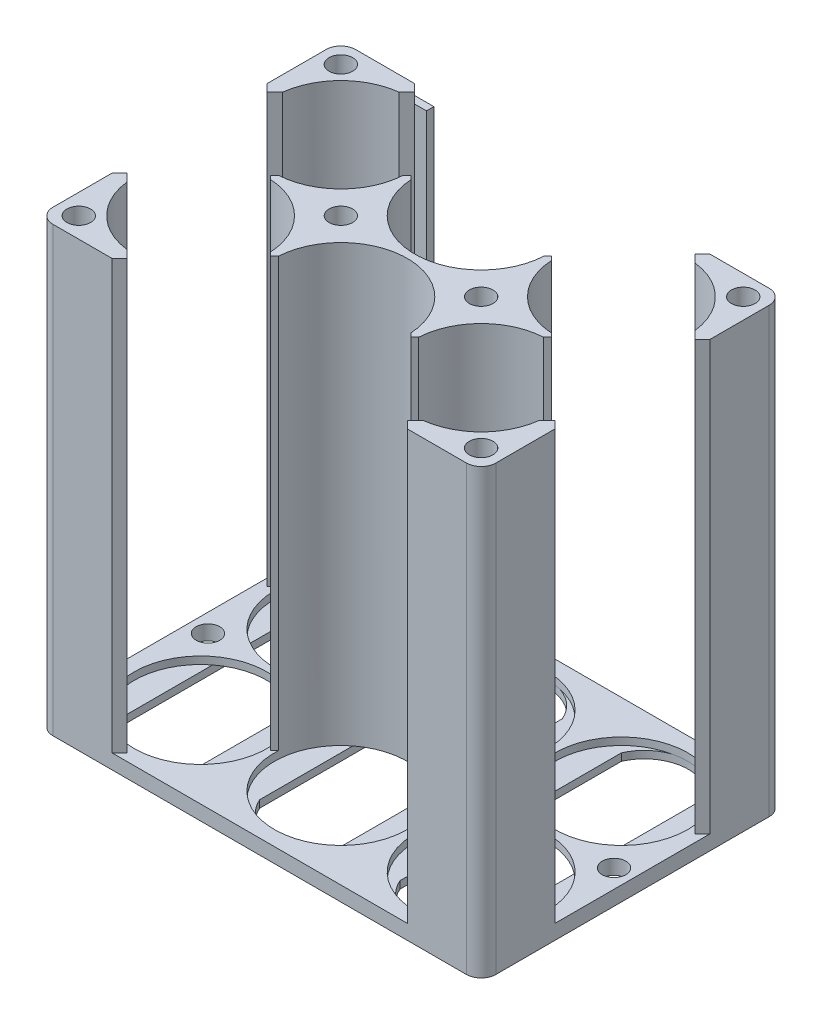
SolidWorks part; units mm, degrees
ref_plane "Płaszczyzna przednia" through (0, 0, 0) normal (0, 0, 1) x (1, 0, 0)
ref_plane "Płaszczyzna górna" through (0, 0, 0) normal (0, 1, 0) x (1, 0, 0)
ref_plane "Płaszczyzna prawa" through (0, 0, 0) normal (1, 0, 0) x (0, 0, -1)
sketch "Sketch1" plane through (0, 0, 0) normal (0, 1, 0) x (1, 0, 0)
  line L1 (0, 0) -> (-60, 0)
  line L2 (0, 0) -> (0, 41)
  line L3 (0, 41) -> (-60, 41)
  line L4 (-60, 0) -> (-60, 41)
  line L5 (0, 0) -> (-60, 41) construction
  line L6 (0, 41) -> (-60, 0) construction
  point P4 (-30, 20.5)
  dimension "D1" = 41
  dimension "D2" = 60
extrude "Boss-Extrude1" add sketch "Sketch1" along normal blind 2
sketch "Sketch2" plane through (0, 2, 0) normal (0, 1, 0) x (1, 0, 0)
  line L0 (-60, 41) -> (-60, 0) construction
  line L1 (-60, 0) -> (0, 0) construction
  circle A0 centre (-49, 11) radius 9
  circle A1 centre (-30, 11) radius 9
  circle A2 centre (-11, 11) radius 9
  circle A3 centre (-30, 30) radius 9
  circle A4 centre (-11, 30) radius 9
  circle A5 centre (-49, 30) radius 9
  dimension "D1" = 18
  dimension "D2" = 11
  dimension "D3" = 11
  dimension "D4" = 3
  dimension "D5" = 2
extrude "Cut-Extrude2" cut sketch "Sketch2" against normal blind 1 contours A0 | A1 | A5 | A3 | A4 | A2
sketch "Sketch3" plane through (0, 0, 0) normal (0, -1, 0) x (1, 0, 0)
  line L0 (0, -41) -> (-60, -41) construction
  line L2 (-5.5, -35.4979) -> (-5.5, -5.4979)
  line L4 (-16.5, -35.4979) -> (-16.5, -5.4979)
  line L5 (-5.5, -35.4979) -> (-16.5, -5.4979) construction
  line L6 (-5.5, -5.4979) -> (-16.5, -35.4979) construction
  line L7 (-60, 0) -> (0, 0) construction
  line L9 (0, 0) -> (0, -41) construction
  line L10 (-35.5, -35.4979) -> (-35.5, -5.4979)
  line L11 (-24.5, -35.4979) -> (-24.5, -5.4979)
  line L12 (-54.5, -35.4979) -> (-54.5, -5.4979)
  line L13 (-43.5, -35.4979) -> (-43.5, -5.4979)
  line L14 (-60, -41) -> (-60, 0) construction
  arc A0 (-5.5, -5.4979) -> (-16.5, -5.4979) centre (-11, -7.8958) ccw
  arc A1 (-5.5, -35.4979) -> (-16.5, -35.4979) centre (-11, -33.1) cw
  arc A2 (-24.5, -5.4979) -> (-35.5, -5.4979) centre (-30, -7.8958) ccw
  arc A3 (-24.5, -35.4979) -> (-35.5, -35.4979) centre (-30, -33.1) cw
  arc A4 (-43.5, -5.4979) -> (-54.5, -5.4979) centre (-49, -7.8958) ccw
  arc A5 (-43.5, -35.4979) -> (-54.5, -35.4979) centre (-49, -33.1) cw
  point P4 (-11, -20.4979)
  dimension "D2" = 6
  dimension "D3" = 6
  dimension "D5" = 7.9
  dimension "D6" = 7.8958
  dimension "D1" = 11
  dimension "D4" = 30
  dimension "D7" = 5.5
  dimension "D9" = 5.5
  dimension "D8" = 3
extrude "Cut-Extrude3" cut sketch "Sketch3" against normal blind 1
sketch "Sketch4" plane through (0, 0, 0) normal (0, -1, 0) x (1, 0, 0)
  line L0 (-16.5, -5.4979) -> (-16.5, -35.4979) construction
  line L1 (-16.5, -24.5011) -> (-24.5, -24.5011)
  line L2 (-16.5, -24.5011) -> (-16.5, -16.5011)
  line L3 (-16.5, -16.5011) -> (-24.5, -16.5011)
  line L4 (-24.5, -24.5011) -> (-24.5, -16.5011)
  line L5 (-16.5, -24.5011) -> (-24.5, -16.5011) construction
  line L6 (-16.5, -16.5011) -> (-24.5, -24.5011) construction
  line L7 (-24.5, -35.4979) -> (-24.5, -5.4979) construction
  point P4 (-20.5, -20.5011)
  dimension "D1" = 8
  dimension "D2" = 1.625
  dimension "D3" = 1.6228
extrude "Cut-Extrude4" cut sketch "Sketch4" against normal blind 1
sketch "Sketch5" plane through (0, 2, 0) normal (0, 1, 0) x (1, 0, 0)
  line L0 (-20, 30) -> (-21, 30)
  line L1 (-11, 21) -> (-11, 20)
  line L2 (-20, 11) -> (-21, 11)
  line L3 (-49, 21) -> (-49, 20)
  line L4 (-39, 11) -> (-40, 11)
  line L5 (-40, 30) -> (-39, 30)
  line L6 (-58, 30) -> (-60, 30)
  line L7 (-60, 41) -> (-60, 0) construction
  line L8 (-60, 30) -> (-60, 41)
  line L9 (-60, 41) -> (-49, 41)
  line L10 (0, 41) -> (-60, 41) construction
  line L11 (-49, 41) -> (-49, 39)
  line L12 (-58, 11) -> (-60, 11)
  line L13 (-60, 11) -> (-60, 0)
  line L14 (-60, 0) -> (-49, 0)
  line L15 (-60, 0) -> (0, 0) construction
  line L16 (-49, 0) -> (-49, 2)
  line L17 (-2, 11) -> (0, 11)
  line L18 (0, 0) -> (0, 41) construction
  line L19 (0, 11) -> (0, 0)
  line L20 (0, 0) -> (-11, 0)
  line L21 (-11, 0) -> (-11, 2)
  line L22 (-2, 30) -> (0, 30)
  line L23 (0, 30) -> (0, 41)
  line L24 (0, 41) -> (-11, 41)
  line L25 (-11, 41) -> (-11, 39)
  arc A0 (-20, 30) -> (-11, 21) centre (-11, 30) ccw
  circle A1 centre (-11, 30) radius 9 construction
  arc A2 (-11, 20) -> (-20, 11) centre (-11, 11) ccw
  circle A3 centre (-11, 11) radius 9 construction
  arc A4 (-21, 11) -> (-30, 20) centre (-30, 11) ccw
  circle A5 centre (-30, 11) radius 9 construction
  arc A6 (-30, 21) -> (-21, 30) centre (-30, 30) ccw
  circle A7 centre (-30, 30) radius 9 construction
  arc A8 (-30, 21) -> (-39, 30) centre (-30, 30) cw
  arc A9 (-39, 11) -> (-30, 20) centre (-30, 11) cw
  arc A10 (-40, 11) -> (-49, 20) centre (-49, 11) ccw
  circle A11 centre (-49, 11) radius 9 construction
  arc A12 (-49, 21) -> (-40, 30) centre (-49, 30) ccw
  circle A13 centre (-49, 30) radius 9 construction
  arc A14 (-2, 11) -> (-11, 2) centre (-11, 11) cw
  arc A15 (-2, 30) -> (-11, 39) centre (-11, 30) ccw
  arc A16 (-49, 39) -> (-58, 30) centre (-49, 30) ccw
  arc A17 (-58, 11) -> (-49, 2) centre (-49, 11) ccw
extrude "Boss-Extrude2" add sketch "Sketch5" along normal blind 58
sketch "Sketch6" plane through (0, 60, 0) normal (0, 1, 0) x (1, 0, 0)
  line L0 (-11, 0) -> (0, 0) construction
  line L1 (0, 0) -> (0, 11) construction
  line L2 (0, 30) -> (0, 41) construction
  line L3 (0, 41) -> (-11, 41) construction
  line L4 (-60, 41) -> (-60, 30) construction
  line L5 (-49, 41) -> (-60, 41) construction
  line L6 (-60, 11) -> (-60, 0) construction
  line L7 (-60, 0) -> (-49, 0) construction
  line L8 (-40, 11) -> (-39, 11) construction
  line L9 (-39, 30) -> (-40, 30) construction
  line L10 (-49, 21) -> (-49, 20) construction
  line L11 (-11, 20) -> (-11, 21) construction
  line L12 (-20, 30) -> (-21, 30) construction
  circle A0 centre (-20.5, 20.5) radius 1.6
  circle A1 centre (-39.5, 20.5) radius 1.6
  circle A2 centre (-57.25, 2.75) radius 1.6
  circle A3 centre (-57.25, 38.25) radius 1.6
  circle A4 centre (-2.75, 2.75) radius 1.6
  circle A5 centre (-2.75, 38.25) radius 1.6
  dimension "D1" = 3.2
  dimension "D2" = 3.2
  dimension "D3" = 3.2
  dimension "D4" = 3.2
  dimension "D5" = 3.2
  dimension "D6" = 3.2
  dimension "D7" = 2.75
  dimension "D8" = 2.75
  dimension "D9" = 2.75
  dimension "D10" = 2.75
  dimension "D11" = 2.75
  dimension "D12" = 2.75
  dimension "D13" = 2.75
  dimension "D14" = 9.5
  dimension "D15" = 9.5
  dimension "D16" = 9.5
  dimension "D17" = 9.5
  dimension "3" = 2.75
  dimension "D18" = 9.5
extrude "Cut-Extrude5" cut sketch "Sketch6" against normal blind 18
chamfer "Chamfer2" distance 0.5 angle 45 12 edges at (-40, 31, -11) (-39, 31, -11) (-21, 31, -11) (-20, 31, -11) (-49, 31, -20) (-49, 31, -21) (-40, 31, -30) (-39, 31, -30) (-21, 31, -30) (-20, 31, -30) (-11, 31, -21) (-11, 31, -20)
chamfer "Chamfer3" distance 1 angle 45 16 edges at (-2, 31, -30) (0, 31, -30) (-11, 31, -39) (-11, 31, -41) (-58, 31, -30) (-60, 31, -30) (-49, 31, -41) (-49, 31, -39) (-60, 31, -11) (-58, 31, -11) (-49, 31, -2) (-49, 31, 0) (-11, 31, -2) (-11, 31, 0) (-2, 31, -11) (0, 31, -11)
sketch "Sketch7" plane through (0, 2, 0) normal (0, 1, 0) x (1, 0, 0)
  line L1 (-60, 31) -> (-60, 10) construction
  line L2 (0, 10) -> (0, 31) construction
  circle A0 centre (-57.5, 20.5) radius 1.6
  circle A1 centre (-2.5, 20.5) radius 1.6
  dimension "D1" = 3.2
  dimension "D2" = 3.2
  dimension "D3" = 2.5
  dimension "D4" = 2.5
  dimension "D5" = 9.5
  dimension "D6" = 9.5
  dimension "D7" = 9.5
  dimension "D8" = 9.5
extrude "Cut-Extrude6" cut sketch "Sketch7" against normal through all
fillet "Fillet1" radius 2 8 edges at (-24.5, 0.5, -24.5011) (-16.5, 0.5, -24.5011) (-24.5, 0.5, -16.5011) (-16.5, 0.5, -16.5011) (0, 30, 0) (0, 30, -41) (-60, 30, -41) (-60, 30, 0)
sketch "Sketch9" plane through (0, 0, -41) normal (0, 0, -1) x (-1, 0, 0)
  line L0 (2, 0) -> (58, 0) construction
  line L1 (52.5, 0) -> (54.5, 0)
  line L2 (52.5, 2) -> (52.5, 56)
  line L3 (52.5, 56) -> (54.5, 56)
  line L4 (54.5, 0) -> (54.5, 56)
  line L5 (52.5, 0) -> (54.5, 56) construction
  line L6 (52.5, 56) -> (54.5, 0) construction
  line L7 (50, 60) -> (50, 2) construction
  line L8 (5.5, 0) -> (7.5, 0)
  line L9 (5.5, 0) -> (5.5, 56)
  line L10 (5.5, 56) -> (7.5, 56)
  line L11 (7.5, 2) -> (7.5, 56)
  line L12 (5.5, 0) -> (7.5, 56) construction
  line L13 (5.5, 56) -> (7.5, 0) construction
  line L14 (10, 2) -> (10, 60) construction
  line L16 (7.5, 0) -> (10, 0)
  line L18 (7.5, 2) -> (10, 2)
  line L19 (10, 0) -> (10, 2)
  line L20 (7.5, 0) -> (10, 2) construction
  line L21 (7.5, 2) -> (10, 0) construction
  line L22 (52.5, 0) -> (50, 0)
  line L24 (52.5, 2) -> (50, 2)
  line L25 (50, 0) -> (50, 2)
  line L26 (52.5, 0) -> (50, 2) construction
  line L27 (52.5, 2) -> (50, 0) construction
  point P4 (53.5, 28)
  point P5 (53.5, 0)
  point P12 (6.5, 28)
  point P20 (8.75, 1)
  point P25 (51.25, 1)
  dimension "D1" = 2
  dimension "D2" = 56
  dimension "D3" = 0
  dimension "D4" = 2
  dimension "D5" = 56
  dimension "D6" = 0
  dimension "D7" = 45
  dimension "D8" = 2.5
  dimension "D9" = 2.5
extrude "Boss-Extrude3" add sketch "Sketch9" along normal blind 2.6
sketch "Sketch11" plane through (0, 2, 0) normal (0, 1, 0) x (1, 0, 0)
  line L0 (-7.5, 43.6) -> (-7.5, 41) construction
  line L1 (-10, 43.6) -> (-7.5, 43.6)
  line L2 (-10, 43.6) -> (-10, 42.6)
  line L3 (-10, 42.6) -> (-7.5, 42.6)
  line L4 (-7.5, 43.6) -> (-7.5, 42.6)
  line L5 (-10, 43.6) -> (-7.5, 42.6) construction
  line L6 (-10, 42.6) -> (-7.5, 43.6) construction
  line L7 (-52.5, 43.6) -> (-52.5, 41) construction
  line L8 (-50, 43.6) -> (-52.5, 43.6)
  line L9 (-50, 43.6) -> (-50, 42.6)
  line L10 (-50, 42.6) -> (-52.5, 42.6)
  line L11 (-52.5, 43.6) -> (-52.5, 42.6)
  line L12 (-50, 43.6) -> (-52.5, 42.6) construction
  line L13 (-50, 42.6) -> (-52.5, 43.6) construction
  point P4 (-8.75, 43.1)
  point P12 (-51.25, 43.1)
  dimension "D1" = 1
  dimension "D2" = 1
extrude "Boss-Extrude4" add sketch "Sketch11" along normal blind 54
fillet "Fillet2" radius 2 2 edges at (-5.5, 28, -43.6) (-54.5, 28, -43.6)
